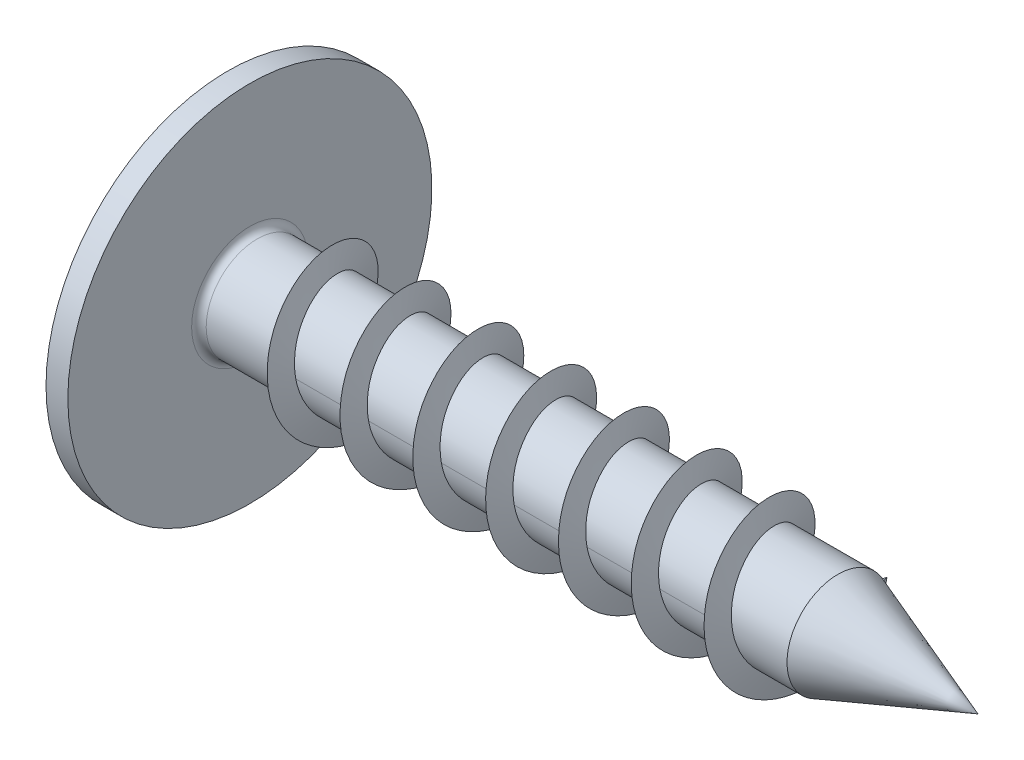
SolidWorks part; units mm, degrees
material "Acier allié"
ref_plane "Plane1" through (0, 0, 0) normal (0, 0, 1) x (1, 0, 0)
ref_plane "Plane2" through (0, 0, 0) normal (0, 1, 0) x (1, 0, 0)
ref_plane "Plane3" through (0, 0, 0) normal (1, 0, 0) x (0, 0, -1)
ref_axis "Axe1" through (0, 0, 0) along (1, 0, 0)
sketch "BodySke" plane through (0, 0, 0) normal (0, 0, 1) x (1, 0, 0)
  line L0 (1.3, 0.7) -> (1.3, 2.5)
  line L1 (1.8, 6.35) -> (1.8, -3.175) construction
  line L2 (-25.4, 0) -> (127, 0) construction
  line L3 (11.3, 0) -> (0, 0)
  line L4 (1.3, 0.7) -> (9.3768, 0.7)
  line L6 (0.6202, 1.75) -> (1, 1.75)
  line L7 (1, 1.75) -> (1, 2.5)
  line L8 (1.3, 6.35) -> (1.3, -3.175) construction
  line L9 (1, 2.5) -> (1.3, 2.5)
  line L10 (11.3, 0) -> (9.3768, 0.7)
  arc A0 (0.4664, 1.6636) -> (0, 0) centre (3.2, 0) ccw
  arc A2 (0.4664, 1.6636) -> (0.6202, 1.75) centre (0.6202, 1.57) cw
  dimension "Head_fillet_rad" = 0.18
  dimension "D3" = 1.3
  dimension "Head_crown_rad" = 3.2
  dimension "D4" = 1.4
  dimension "D1" = 5
  dimension "D2" = 0.3
  dimension "Head_dia" = 3.5
  dimension "D5" = 20
  dimension "D6" = 10
  dimension "D7" = 0.5
revolve "Base-Revolve" add sketch "BodySke" angle 360 about L2
fillet "Fillet1" radius 0.1 1 edges at (1.3, 0, 0.7)
sketch "Sketch3" plane through (0, 0, 0) normal (1, 0, 0) x (0, 0, -1)
  line L0 (0.24, -1.05) -> (-0.24, -1.05)
  line L1 (0.24, -1.05) -> (0.24, 1.05)
  line L2 (-0.24, 1.05) -> (0.24, 1.05)
  line L3 (-0.24, 1.05) -> (-0.24, -1.05)
  dimension "D1" = 1.05
  dimension "Cross_dia" = 2.1
  dimension "D2" = 0.24
  dimension "Cross_width" = 0.48
ref_plane "Plane4" through (1.42, 0, 0) normal (1, 0, 0) x (0, 0, -1)
sketch "Sketch4" plane through (1.42, 0, 0) normal (1, 0, 0) x (0, 0, -1)
  line L0 (0.24, -0.342) -> (-0.24, -0.342)
  line L1 (0.24, -0.342) -> (0.24, 0.342)
  line L2 (-0.24, 0.342) -> (0.24, 0.342)
  line L3 (-0.24, 0.342) -> (-0.24, -0.342)
  dimension "D1" = 0.48
  dimension "D2" = 0.684
  dimension "D3" = 0.24
  dimension "D4" = 0.342
loft "Recess" cut profiles "Sketch3", "Sketch4"
pattern_circular "RecPat" count 2 every 90 about axis through (-25.4, 0, 0) along (1, 0, 0) of "Recess"
sketch "RecCorSke" plane through (0, 0, 0) normal (0, 0, 1) x (1, 0, 0)
  line L0 (-3.175, 0) -> (15.875, 0) construction
  line L1 (-25.4, 0) -> (127, 0) construction
  line L2 (0, 0) -> (0, 0.4548)
  line L3 (0, 0.4548) -> (1.42, 0.3555)
  line L4 (1.42, 0.3555) -> (1.5355, 0)
  line L5 (1.5355, 0) -> (0, 0)
  dimension "Diameter" = 0.711
  dimension "Depth" = 1.42
  dimension "Draft_angle" = 4
  dimension "Bottom_angle" = 18
revolve "RecessCore" cut sketch "RecCorSke" angle 360 about L0
ref_plane "Plan1" through (1.8, 0, 0) normal (-1, 0, 0) x (0, -1, 0)
sketch "Esquisse1" plane through (1.8, 0, 0) normal (-1, 0, 0) x (0, -1, 0)
  circle A0 centre (0, 0) radius 1
  dimension "D1" = 2
curve "Hélice/Spirale1" pitch 1 height 7.25 radius 1 centre (1.8, 0, 0) axis (1, 0, 0) start towards (0, -1, 0)
sketch "Esquisse2" plane through (0, 0, 0) normal (0, 0, 1) x (1, 0, 0)
  line L0 (1.7196, -0.7) -> (1.8, -1)
  line L1 (1.8, -1) -> (1.8804, -0.7)
  line L2 (1.7196, -0.7) -> (1.8804, -0.7)
  line L3 (1.4, -0.7) -> (9.3768, -0.7) construction
  dimension "D1" = 30
sweep "Balayage1" add profiles "Esquisse2" path "Hélice/Spirale1"
